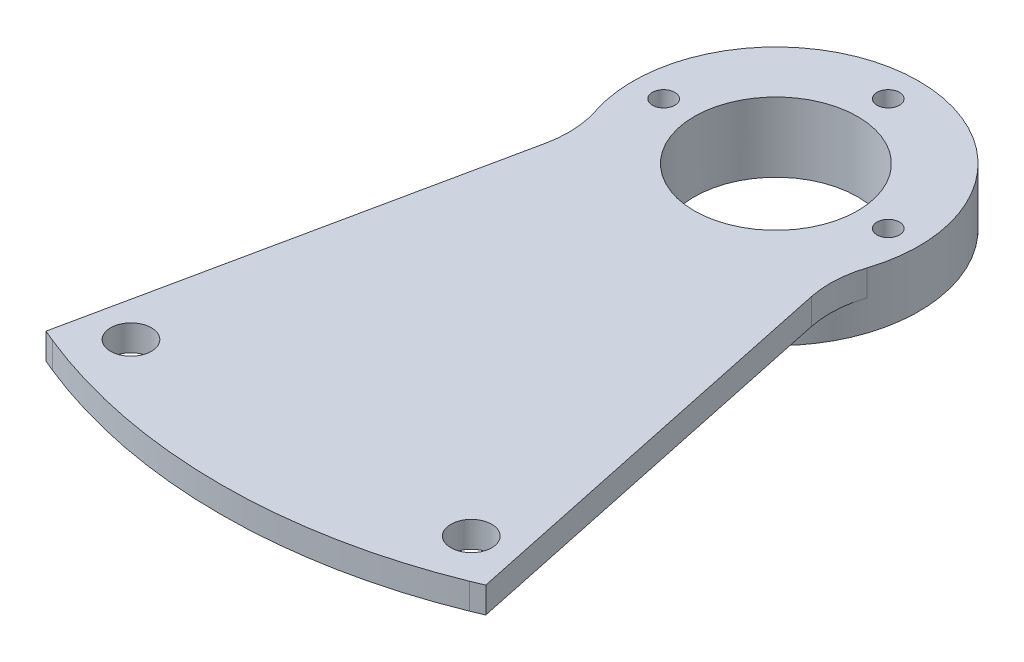
SolidWorks part; units mm, degrees
ref_plane "Front Plane" through (0, 0, 0) normal (0, 0, 1) x (1, 0, 0)
ref_plane "Top Plane" through (0, 0, 0) normal (0, 1, 0) x (1, 0, 0)
ref_plane "Right Plane" through (0, 0, 0) normal (1, 0, 0) x (0, 0, -1)
sketch "Sketch1" plane through (0, 0, 0) normal (0, 1, 0) x (1, 0, 0)
  line L0 (7.2, -9.7213) -> (0, -9.7213) construction
  line L1 (21.5362, -59.6749) -> (20.4111, -60.1451)
  line L2 (-21.5362, -59.6749) -> (-20.4111, -60.1451)
  line L5 (19.421, -49.6466) -> (11, -9.7213)
  line L6 (-19.421, -49.6466) -> (-11, -9.7213)
  line L7 (4.5, -9.7213) -> (8, -9.7213) construction
  line L8 (8, -9.7213) -> (14, -9.7213) construction
  line L10 (-0.0056, -54.1196) -> (-0.0012, -57.1196) construction
  line L11 (-0.0012, -57.1196) -> (-0.0003, -61.1196) construction
  line L12 (-0.0003, -61.1196) -> (0, -64.1196) construction
  line L13 (-0.0012, -57.1196) -> (-0.0003, -61.1196) construction
  line L15 (0, -9.7213) -> (-20.4111, -60.1451) construction
  line L16 (0, -9.7213) -> (20.4111, -60.1451) construction
  line L17 (19.421, -49.6466) -> (21.5362, -59.6749)
  line L18 (-19.421, -49.6466) -> (-21.5362, -59.6749)
  line L19 (-20.4111, -60.1451) -> (-16.659, -50.8757)
  line L20 (20.4111, -60.1451) -> (16.659, -50.8757)
  circle A4 centre (0, -9.7213) radius 8
  arc A9 (0, -64.1196) -> (20.4111, -60.1451) centre (0, -9.7213) ccw
  arc A11 (0, -64.1196) -> (-20.4111, -60.1451) centre (0, -9.7213) cw
  circle A16 centre (0, -9.7213) radius 8
  circle A17 centre (0, -9.7213) radius 14
  circle A18 centre (11, -9.7213) radius 1.1
  circle A20 centre (-11, -9.7213) radius 1.1
  circle A21 centre (0, 1.2787) radius 1.1
  circle A26 centre (0, -9.7213) radius 6
  circle A27 centre (16.666, -56.2233) radius 2
  circle A29 centre (-16.666, -56.2233) radius 2
  point P35 (0, -9.7213)
  point P37 (0, -9.7213)
  point P62 (0, -9.7213)
  dimension "D1" = 44.075
extrude "Boss-Extrude1" add sketch "Sketch1" along normal blind 2.54 contours A16 | L5 L6 | A11 A9 | L5 L6 | L19 L18 L2 | A29 L19 | A29 L19 | L17 L20 L1 | A27 L20 | A27 L20 region at (0, 0, 43.4345) region at (0, 0, 23.3253)
fillet "Fillet2" radius 10 2 edges at (-12.3792, 1.27, 16.2601) (12.3792, 1.27, 16.2601)
extrude "Boss-Extrude2" add sketch "Sketch1<4>" against normal blind 3 contours A20 A17 A18 A21 A4 region at (0, 0, 23.3253)
sketch "Sketch1<4>" plane through (0, 0, 0) normal (0, 1, 0) x (1, 0, 0) same geometry as "Sketch1"
sketch "Sketch2" plane through (0, -3, 0) normal (0, -1, 0) x (1, 0, 0)
  circle A0 centre (0, 9.7213) radius 9
  circle A1 centre (0, 9.7213) radius 8
extrude "Boss-Extrude3" add sketch "Sketch2" along normal blind 1.27
